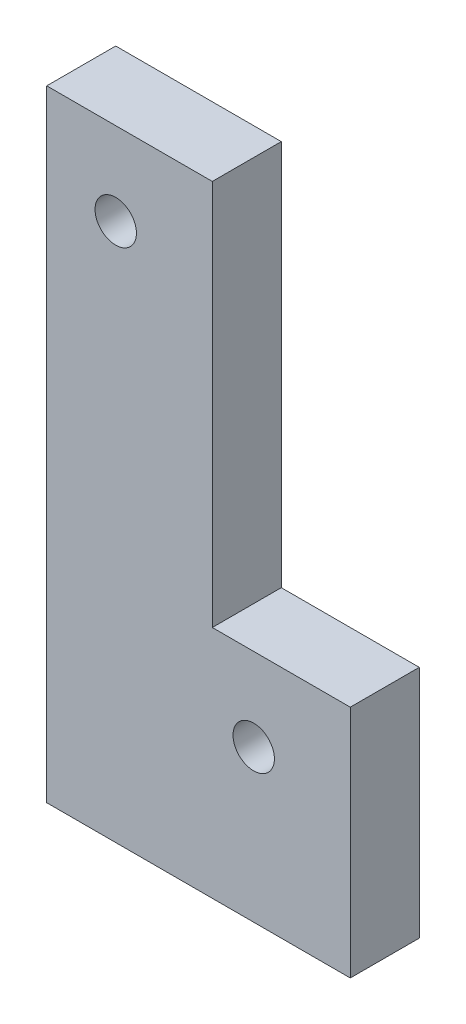
SolidWorks part; units mm, degrees
ref_plane "Plan de face" through (0, 0, 0) normal (0, 0, 1) x (1, 0, 0)
ref_plane "Plan de dessus" through (0, 0, 0) normal (0, 1, 0) x (1, 0, 0)
ref_plane "Plan de droite" through (0, 0, 0) normal (1, 0, 0) x (0, 0, -1)
sketch "Esquisse1" plane through (0, 0, 0) normal (0, 0, 1) x (1, 0, 0)
  line L1 (0, 0) -> (22, 0)
  line L2 (0, 0) -> (0, 45)
  line L3 (0, 45) -> (12, 45)
  line L4 (22, 0) -> (22, 17)
  line L6 (12, 45) -> (12, 17)
  line L7 (12, 17) -> (22, 17)
  circle A0 centre (5, 39) radius 1.5
  circle A1 centre (15, 11) radius 1.5
  dimension "D3" = 28
  dimension "D4" = 3
  dimension "D1" = 22
  dimension "D2" = 45
  dimension "D5" = 6
  dimension "D6" = 5
  dimension "D7" = 15
  dimension "D8" = 10
  dimension "D9" = 28
extrude "Boss.-Extru.1" add sketch "Esquisse1" along normal blind 5
